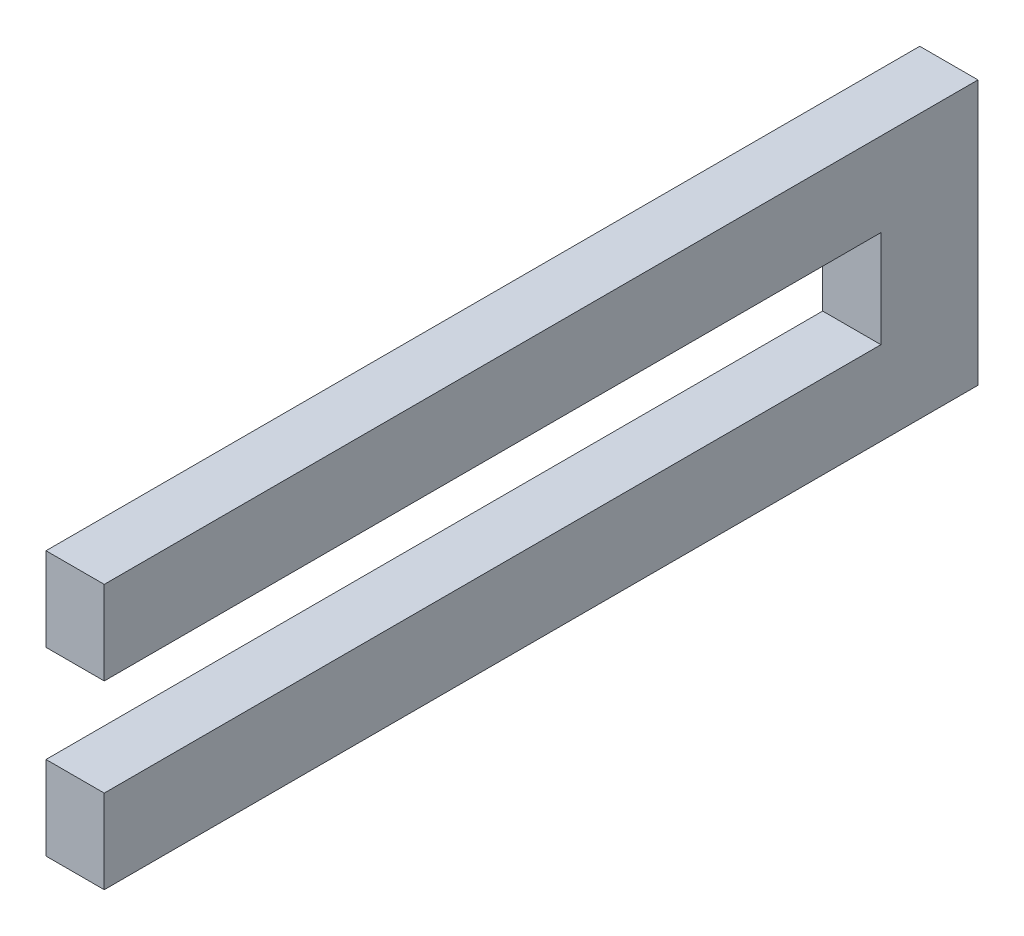
SolidWorks part; units mm, degrees
material "Custom Plastic"
ref_plane "Front Plane" through (0, 0, 0) normal (0, 0, 1) x (1, 0, 0)
ref_plane "Top Plane" through (0, 0, 0) normal (0, 1, 0) x (1, 0, 0)
ref_plane "Right Plane" through (0, 0, 0) normal (1, 0, 0) x (0, 0, -1)
sketch "Sketch2" plane through (0, 0, 0) normal (1, 0, 0) x (0, 0, -1)
  line L0 (-20.4527, -4.3885) -> (24.5473, -4.3885)
  line L1 (24.5473, -4.3885) -> (24.5473, -18.0092)
  line L2 (24.5473, -18.0092) -> (-20.4527, -18.0092)
  line L3 (-20.4527, -18.0092) -> (-20.4527, -13.6989)
  line L4 (-20.4527, -13.6989) -> (19.5473, -13.6989)
  line L5 (19.5473, -13.6989) -> (19.5473, -8.6989)
  line L6 (19.5473, -8.6989) -> (-20.4527, -8.6989)
  line L7 (-20.4527, -8.6989) -> (-20.4527, -4.3885)
  dimension "D1" = 5
  dimension "D2" = 40
  dimension "D3" = 45
extrude "Boss-Extrude1" add sketch "Sketch2" along normal blind 3
